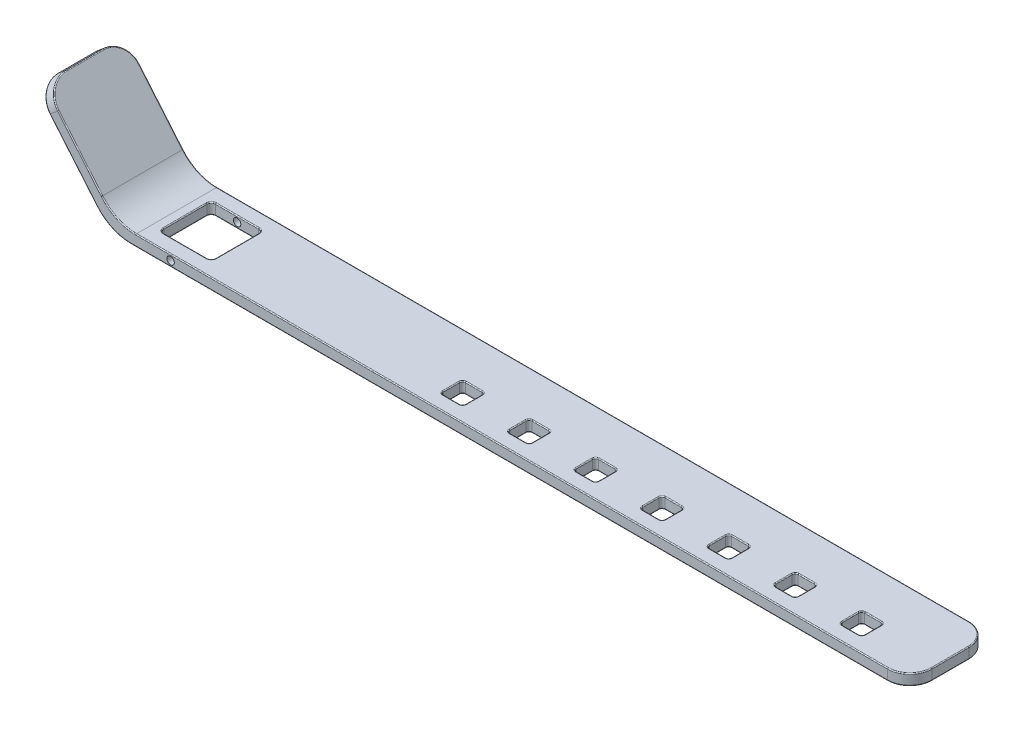
SolidWorks part; units mm, degrees
ref_plane "Front Plane" through (0, 0, 0) normal (0, 0, 1) x (1, 0, 0)
ref_plane "Top Plane" through (0, 0, 0) normal (0, 1, 0) x (1, 0, 0)
ref_plane "Right Plane" through (0, 0, 0) normal (1, 0, 0) x (0, 0, -1)
sketch "Sketch1" plane through (0, 0, 0) normal (0, 0, 1) x (1, 0, 0)
  line L0 (-98.5968, 5.7865) -> (-114.2836, 24.4813)
  line L1 (-89.4043, 1.5) -> (120, 1.5)
  line L3 (-90.8032, -1.5) -> (120, -1.5)
  line L4 (120, 1.5) -> (120, -1.5)
  line L5 (-114.2836, 24.4813) -> (-116.5818, 22.553)
  line L6 (-116.5818, 22.553) -> (-99.9958, 2.7865)
  circle A0 centre (-80, 0) radius 1
  arc A1 (-89.4043, 1.5) -> (-98.5968, 5.7865) centre (-89.4043, 13.5) cw
  arc A2 (-90.8032, -1.5) -> (-99.9958, 2.7865) centre (-90.8032, 10.5) cw
  point P4 (-80, 0)
  point P12 (-95, 1.5)
  dimension "D7" = 2
  dimension "D2" = 12
  dimension "D12" = 12
  dimension "D1" = 215
  dimension "D3" = 1.5
  dimension "D4" = 120
  dimension "D5" = 1.5
  dimension "D6" = 200
  dimension "D8" = 130
  dimension "D9" = 30
  dimension "D10" = 3
  dimension "D11" = 90
extrude "Boss-Extrude1" add sketch "Sketch1" along normal blind 11 and the other way blind 11
fillet "Fillet1" radius 6 4 edges at (-115.4327, 23.5172, -11) (-115.4327, 23.5172, 11) (120, 0, 11) (120, 0, -11)
sketch "Sketch2" plane through (0, 1.5, 0) normal (0, 1, 0) x (1, 0, 0)
  line L0 (114, -11) -> (-89.4043, -11) construction
  line L1 (-85.8, 7) -> (-74.2, 7)
  line L2 (-87, 5.8) -> (-87, -5.8)
  line L3 (-85.8, -7) -> (-74.2, -7)
  line L4 (-73, 5.8) -> (-73, -5.8)
  line L5 (120, 5) -> (120, -5) construction
  line L6 (79.8, -1) -> (84.2, -1)
  line L7 (97.8, -1) -> (102.2, -1)
  line L8 (97, -1.8) -> (97, -6.2)
  line L9 (97.8, -7) -> (102.2, -7)
  line L10 (103, -1.8) -> (103, -6.2)
  line L11 (85, -1.8) -> (85, -6.2)
  line L12 (79.8, -7) -> (84.2, -7)
  line L13 (79, -1.8) -> (79, -6.2)
  line L14 (61.8, -1) -> (66.2, -1)
  line L15 (67, -1.8) -> (67, -6.2)
  line L16 (61.8, -7) -> (66.2, -7)
  line L17 (61, -1.8) -> (61, -6.2)
  line L18 (43.8, -1) -> (48.2, -1)
  line L19 (49, -1.8) -> (49, -6.2)
  line L20 (43.8, -7) -> (48.2, -7)
  line L21 (43, -1.8) -> (43, -6.2)
  line L22 (25.8, -1) -> (30.2, -1)
  line L23 (31, -1.8) -> (31, -6.2)
  line L24 (25.8, -7) -> (30.2, -7)
  line L25 (25, -1.8) -> (25, -6.2)
  line L26 (7.8, -1) -> (12.2, -1)
  line L27 (13, -1.8) -> (13, -6.2)
  line L28 (7.8, -7) -> (12.2, -7)
  line L29 (7, -1.8) -> (7, -6.2)
  line L30 (-10.2, -1) -> (-5.8, -1)
  line L31 (-5, -1.8) -> (-5, -6.2)
  line L32 (-10.2, -7) -> (-5.8, -7)
  line L33 (-11, -1.8) -> (-11, -6.2)
  arc A0 (-85.8, -7) -> (-87, -5.8) centre (-85.8, -5.8) cw
  arc A1 (-74.2, -7) -> (-73, -5.8) centre (-74.2, -5.8) ccw
  arc A2 (-73, 5.8) -> (-74.2, 7) centre (-74.2, 5.8) ccw
  arc A3 (-85.8, 7) -> (-87, 5.8) centre (-85.8, 5.8) ccw
  arc A4 (103, -1.8) -> (102.2, -1) centre (102.2, -1.8) ccw
  arc A5 (103, -6.2) -> (102.2, -7) centre (102.2, -6.2) cw
  arc A6 (97.8, -7) -> (97, -6.2) centre (97.8, -6.2) cw
  arc A7 (97, -1.8) -> (97.8, -1) centre (97.8, -1.8) cw
  arc A8 (85, -1.8) -> (84.2, -1) centre (84.2, -1.8) ccw
  arc A9 (85, -6.2) -> (84.2, -7) centre (84.2, -6.2) cw
  arc A10 (79.8, -7) -> (79, -6.2) centre (79.8, -6.2) cw
  arc A11 (79, -1.8) -> (79.8, -1) centre (79.8, -1.8) cw
  arc A12 (67, -1.8) -> (66.2, -1) centre (66.2, -1.8) ccw
  arc A13 (67, -6.2) -> (66.2, -7) centre (66.2, -6.2) cw
  arc A14 (61.8, -7) -> (61, -6.2) centre (61.8, -6.2) cw
  arc A15 (61, -1.8) -> (61.8, -1) centre (61.8, -1.8) cw
  arc A16 (49, -1.8) -> (48.2, -1) centre (48.2, -1.8) ccw
  arc A17 (49, -6.2) -> (48.2, -7) centre (48.2, -6.2) cw
  arc A18 (43.8, -7) -> (43, -6.2) centre (43.8, -6.2) cw
  arc A19 (43, -1.8) -> (43.8, -1) centre (43.8, -1.8) cw
  arc A20 (31, -1.8) -> (30.2, -1) centre (30.2, -1.8) ccw
  arc A21 (31, -6.2) -> (30.2, -7) centre (30.2, -6.2) cw
  arc A22 (25.8, -7) -> (25, -6.2) centre (25.8, -6.2) cw
  arc A23 (25, -1.8) -> (25.8, -1) centre (25.8, -1.8) cw
  arc A24 (13, -1.8) -> (12.2, -1) centre (12.2, -1.8) ccw
  arc A25 (13, -6.2) -> (12.2, -7) centre (12.2, -6.2) cw
  arc A26 (7.8, -7) -> (7, -6.2) centre (7.8, -6.2) cw
  arc A27 (7, -1.8) -> (7.8, -1) centre (7.8, -1.8) cw
  arc A28 (-5, -1.8) -> (-5.8, -1) centre (-5.8, -1.8) ccw
  arc A29 (-5, -6.2) -> (-5.8, -7) centre (-5.8, -6.2) cw
  arc A30 (-10.2, -7) -> (-11, -6.2) centre (-10.2, -6.2) cw
  arc A31 (-11, -1.8) -> (-10.2, -1) centre (-10.2, -1.8) cw
  point P12 (-73, -7)
  point P15 (-73, 7)
  point P18 (-87, 7)
  point P23 (100, -7)
  point P26 (103, -1)
  point P31 (97, -7)
  point P34 (97, -1)
  dimension "D5" = 1.2
  dimension "D10" = 0.8
  dimension "D1" = 14
  dimension "D2" = 14
  dimension "D3" = 4
  dimension "D4" = 193
  dimension "D6" = 6
  dimension "D7" = 6
  dimension "D8" = 17
  dimension "D9" = 4
extrude "Cut-Extrude1" cut sketch "Sketch2" against normal up to next
fillet "Fillet2" radius 0.25 152 edges at (-95.8747, -0.3757, -11) (-95.8747, -0.3757, 11) (-94.4757, 2.6243, -11) (-94.4757, 2.6243, 11) (-115.4522, 21.2068, 9.2426) (-106.3604, 10.3716, 11) (-106.3604, 10.3716, -11) (-115.4522, 21.2068, -9.2426) (-116.5818, 22.553, 0) (-104.5119, 12.8358, 11) (-113.154, 23.1351, 9.2426) (-114.2836, 24.4813, 0) (-113.154, 23.1351, -9.2426) (-104.5119, 12.8358, -11) (-86.6485, -1.5, -6.6485) (-80, -1.5, -7) (-73.3515, -1.5, -6.6485) (-73, -1.5, 0) (-73.3515, -1.5, 6.6485) (-80, -1.5, 7) (-86.6485, -1.5, 6.6485) (-87, -1.5, 0) (118.2426, -1.5, -9.2426) (11.5984, -1.5, -11) (11.5984, -1.5, 11) (118.2426, -1.5, 9.2426) (120, -1.5, 0) (-5, -1.5, 4) (-5.2343, -1.5, 6.7657) (-8, -1.5, 7) (-10.7657, -1.5, 6.7657) (-11, -1.5, 4) (-10.7657, -1.5, 1.2343) (-8, -1.5, 1) (-5.2343, -1.5, 1.2343) (13, -1.5, 4) (12.7657, -1.5, 6.7657) (10, -1.5, 7) (7.2343, -1.5, 6.7657) (7, -1.5, 4) (7.2343, -1.5, 1.2343) (10, -1.5, 1) (12.7657, -1.5, 1.2343) (31, -1.5, 4) (30.7657, -1.5, 6.7657) (28, -1.5, 7) (25.2343, -1.5, 6.7657) (25, -1.5, 4) (25.2343, -1.5, 1.2343) (28, -1.5, 1) (30.7657, -1.5, 1.2343) (49, -1.5, 4) (48.7657, -1.5, 6.7657) (46, -1.5, 7) (43.2343, -1.5, 6.7657) (43, -1.5, 4) (43.2343, -1.5, 1.2343) (46, -1.5, 1) (48.7657, -1.5, 1.2343) (67, -1.5, 4) (66.7657, -1.5, 6.7657) (64, -1.5, 7) (61.2343, -1.5, 6.7657) (61, -1.5, 4) (61.2343, -1.5, 1.2343) (64, -1.5, 1) (66.7657, -1.5, 1.2343) (85, -1.5, 4) (84.7657, -1.5, 6.7657) (82, -1.5, 7) (79.2343, -1.5, 6.7657) (79, -1.5, 4) (79.2343, -1.5, 1.2343) (82, -1.5, 1) (84.7657, -1.5, 1.2343) (103, -1.5, 4) (102.7657, -1.5, 6.7657) (100, -1.5, 7) (97.2343, -1.5, 6.7657) (97, -1.5, 4) (97.2343, -1.5, 1.2343) (100, -1.5, 1) (102.7657, -1.5, 1.2343) (12.2978, 1.5, -11) (118.2426, 1.5, -9.2426) (120, 1.5, 0) (118.2426, 1.5, 9.2426) (12.2978, 1.5, 11) (-8, 1.5, 1) (-10.7657, 1.5, 1.2343) (-11, 1.5, 4) (-10.7657, 1.5, 6.7657) (-8, 1.5, 7) (-5.2343, 1.5, 6.7657) (-5, 1.5, 4) (-5.2343, 1.5, 1.2343) (10, 1.5, 1) (7.2343, 1.5, 1.2343) (7, 1.5, 4) (7.2343, 1.5, 6.7657) (10, 1.5, 7) (12.7657, 1.5, 6.7657) (13, 1.5, 4) (12.7657, 1.5, 1.2343) (28, 1.5, 1) (25.2343, 1.5, 1.2343) (25, 1.5, 4) (25.2343, 1.5, 6.7657) (28, 1.5, 7) (30.7657, 1.5, 6.7657) (31, 1.5, 4) (30.7657, 1.5, 1.2343) (46, 1.5, 1) (43.2343, 1.5, 1.2343) (43, 1.5, 4) (43.2343, 1.5, 6.7657) (46, 1.5, 7) (48.7657, 1.5, 6.7657) (49, 1.5, 4) (48.7657, 1.5, 1.2343) (64, 1.5, 1) (61.2343, 1.5, 1.2343) (61, 1.5, 4) (61.2343, 1.5, 6.7657) (64, 1.5, 7) (66.7657, 1.5, 6.7657) (67, 1.5, 4) (66.7657, 1.5, 1.2343) (82, 1.5, 1) (79.2343, 1.5, 1.2343) (79, 1.5, 4) (79.2343, 1.5, 6.7657) (82, 1.5, 7) (84.7657, 1.5, 6.7657) (85, 1.5, 4) (84.7657, 1.5, 1.2343) (100, 1.5, 1) (97.2343, 1.5, 1.2343) (97, 1.5, 4) (97.2343, 1.5, 6.7657) (100, 1.5, 7) (102.7657, 1.5, 6.7657) (103, 1.5, 4) (102.7657, 1.5, 1.2343) (-80, 1.5, 7) (-73.3515, 1.5, 6.6485) (-73, 1.5, 0) (-73.3515, 1.5, -6.6485) (-80, 1.5, -7) (-86.6485, 1.5, -6.6485) (-87, 1.5, 0) (-86.6485, 1.5, 6.6485)
